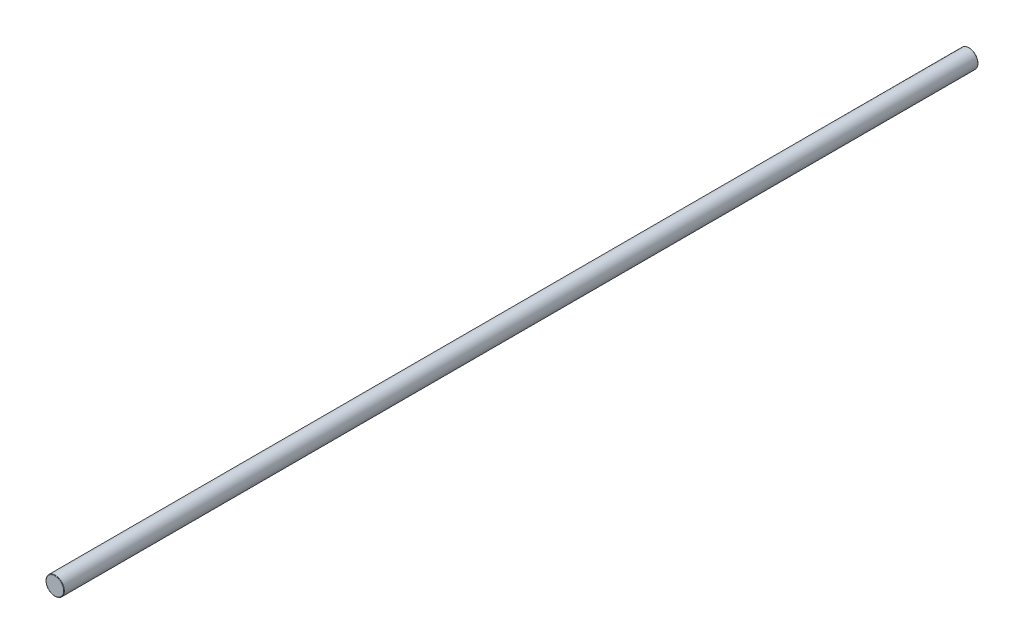
SolidWorks part; units mm, degrees
ref_plane "Front Plane" through (0, 0, 0) normal (0, 0, 1) x (1, 0, 0)
ref_plane "Top Plane" through (0, 0, 0) normal (0, 1, 0) x (1, 0, 0)
ref_plane "Right Plane" through (0, 0, 0) normal (1, 0, 0) x (0, 0, -1)
sketch "Sketch1" plane through (0, 0, 0) normal (0, 0, 1) x (1, 0, 0)
  circle A0 centre (0, 0) radius 4
  dimension "D1" = 8
extrude "Boss-Extrude1" add sketch "Sketch1" against normal blind 400
fillet "Fillet1" radius 0.2 2 edges at (4, 0, -400) (4, 0, 0)
sketch "Sketch2" plane through (0, 0, 0) normal (0, 0, 1) x (1, 0, 0)
  circle A0 centre (0, 0) radius 4
  dimension "D1" = 8
sketch "Sketch3" plane through (0, 0, 0) normal (0, 1, 0) x (1, 0, 0)
  line L0 (3, 0.35) -> (3, 0.05)
  line L1 (3, 0.05) -> (5, -0.75)
  line L2 (5, -0.75) -> (5, 1.15)
  line L3 (5, 1.15) -> (3, 0.35)
  line L4 (5, 0.2) -> (3, 0.2)
  line L7 (4, 0.2) -> (-4, 0.2) construction
  point P7 (4, 0.2)
  dimension "D1" = 1.9
  dimension "D2" = 2
  dimension "D3" = 0.3
  dimension "D4" = 4
curve "Helix/Spiral1" pitch 2 height 400 turns 200
